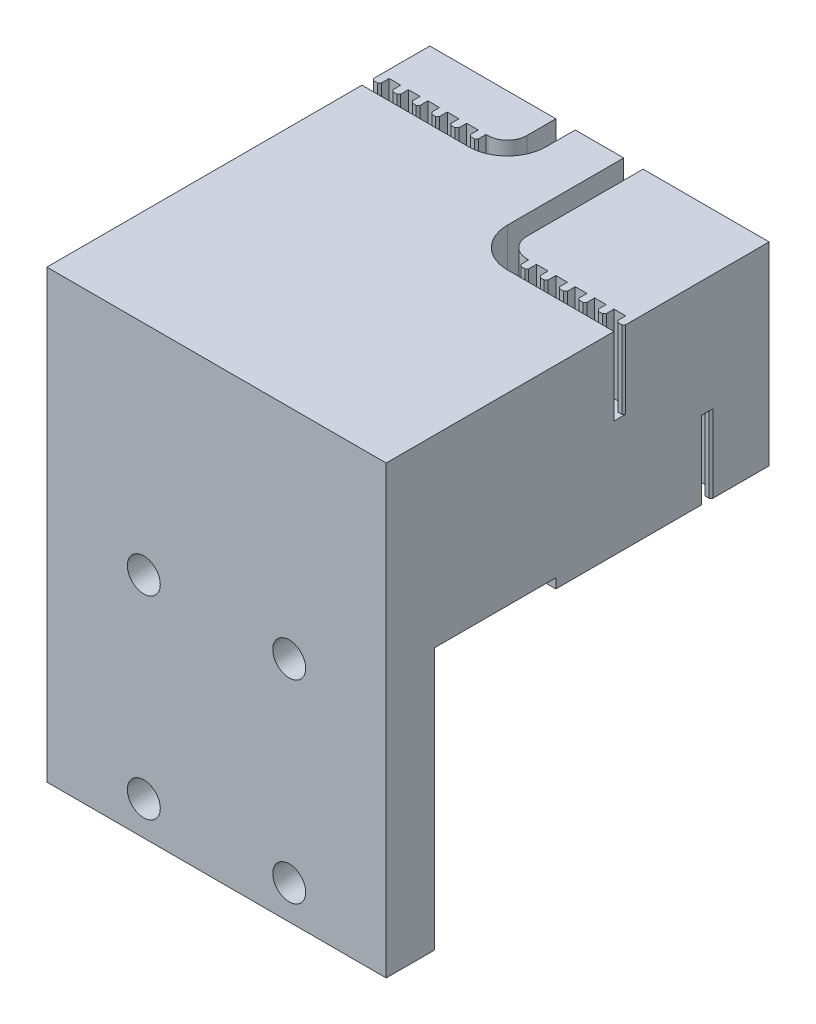
SolidWorks part; units mm, degrees
ref_plane "Front Plane" through (0, 0, 0) normal (0, 0, 1) x (1, 0, 0)
ref_plane "Top Plane" through (0, 0, 0) normal (0, 1, 0) x (1, 0, 0)
ref_plane "Right Plane" through (0, 0, 0) normal (1, 0, 0) x (0, 0, -1)
sketch "Sketch1" plane through (0, 0, 0) normal (0, 1, 0) x (1, 0, 0)
  line L1 (0, 0) -> (35, 0)
  line L2 (0, 0) -> (0, 22)
  line L3 (0, 22) -> (35, 22)
  line L4 (35, 0) -> (35, 22)
  dimension "D1" = 22
  dimension "D2" = 35
extrude "Boss-Extrude1" add sketch "Sketch1" along normal blind 20
sketch "Sketch2" plane through (0, 20, 0) normal (0, 1, 0) x (1, 0, 0)
  line L0 (0, 15) -> (11, 15)
  line L1 (0, 22) -> (0, 0) construction
  line L2 (15, 19) -> (15, 22)
  line L3 (35, 22) -> (0, 22) construction
  line L4 (0, 17) -> (11, 17)
  line L5 (13, 19) -> (13, 22)
  line L6 (35, 6) -> (24, 6)
  line L7 (35, 0) -> (35, 22) construction
  line L8 (20, 10) -> (20, 22)
  line L9 (0, 0) -> (35, 0) construction
  line L10 (22, 22) -> (22, 10)
  line L11 (24, 8) -> (35, 8)
  line L12 (35, 8) -> (35, 6)
  line L13 (0, 15) -> (0, 17)
  line L14 (13, 22) -> (15, 22)
  line L15 (20, 22) -> (22, 22)
  arc A0 (15, 19) -> (11, 15) centre (11, 19) cw
  arc A1 (13, 19) -> (11, 17) centre (11, 19) cw
  arc A2 (20, 10) -> (24, 6) centre (24, 10) ccw
  arc A3 (22, 10) -> (24, 8) centre (24, 10) ccw
  point P9 (15, 15)
  point P15 (13, 17)
  point P29 (20, 6)
  point P32 (22, 8)
  dimension "D3" = 4
  dimension "D6" = 2
  dimension "D11" = 4
  dimension "D12" = 2
  dimension "D1" = 15
  dimension "D2" = 7
  dimension "D4" = 5
  dimension "D5" = 13
  dimension "D7" = 15
  dimension "D8" = 6
  dimension "D9" = 13
  dimension "D10" = 2
extrude "Cut-Extrude1" cut sketch "Sketch2" against normal blind 8
sketch "Sketch5" plane through (0, 0, 0) normal (0, -1, 0) x (-1, 0, 0)
  line L0 (-35, 15) -> (-24, 15)
  line L2 (-20, 19) -> (-20, 22)
  line L4 (-35, 17) -> (-24, 17)
  line L5 (-22, 19) -> (-22, 22)
  line L6 (0, 6) -> (-11, 6)
  line L8 (-15, 10) -> (-15, 22)
  line L10 (-13, 22) -> (-13, 10)
  line L11 (-11, 8) -> (0, 8)
  line L12 (0, 8) -> (0, 6)
  line L13 (-35, 15) -> (-35, 17)
  line L14 (-22, 22) -> (-20, 22)
  line L15 (-15, 22) -> (-13, 22)
  line L16 (-35, 0) -> (-35, 22) construction
  line L17 (-35, 22) -> (0, 22) construction
  line L18 (0, 22) -> (0, 0) construction
  line L19 (0, 0) -> (-35, 0) construction
  arc A0 (-20, 19) -> (-24, 15) centre (-24, 19) cw
  arc A1 (-22, 19) -> (-24, 17) centre (-24, 19) cw
  arc A2 (-15, 10) -> (-11, 6) centre (-11, 10) ccw
  arc A3 (-13, 10) -> (-11, 8) centre (-11, 10) ccw
  point P9 (-20, 15)
  point P15 (-22, 17)
  point P29 (-15, 6)
  point P32 (-13, 8)
  dimension "D3" = 4
  dimension "D6" = 2
  dimension "D11" = 4
  dimension "D12" = 2
  dimension "D1" = 15
  dimension "D2" = 7
  dimension "D4" = 5
  dimension "D5" = 13
  dimension "D7" = 15
  dimension "D8" = 0
  dimension "D9" = 13
  dimension "D10" = 2
  dimension "D13" = 0
  dimension "D14" = 0
  dimension "D15" = 0
  dimension "D16" = 6
extrude "Cut-Extrude2" cut sketch "Sketch5" against normal blind 8
sketch "Sketch6" plane through (0, 20, 0) normal (0, 1, 0) x (1, 0, 0)
  line L0 (0.2, 16) -> (0, 16.2)
  line L1 (0, 17) -> (0.8, 17)
  line L2 (0, 17) -> (0, 16.2)
  line L3 (0.2, 16) -> (0.6, 16)
  line L4 (0.8, 17) -> (0.8, 16.2)
  line L5 (0.6, 16) -> (0.8, 16.2)
  line L6 (2.2, 16) -> (2, 16.2)
  line L7 (2, 17) -> (2.8, 17)
  line L8 (2, 17) -> (2, 16.2)
  line L9 (2.2, 16) -> (2.6, 16)
  line L10 (2.8, 17) -> (2.8, 16.2)
  line L11 (2.6, 16) -> (2.8, 16.2)
  line L12 (4.2, 16) -> (4, 16.2)
  line L13 (4, 17) -> (4.8, 17)
  line L14 (4, 17) -> (4, 16.2)
  line L15 (4.2, 16) -> (4.6, 16)
  line L16 (4.8, 17) -> (4.8, 16.2)
  line L17 (4.6, 16) -> (4.8, 16.2)
  line L18 (6.2, 16) -> (6, 16.2)
  line L19 (6, 17) -> (6.8, 17)
  line L20 (6, 17) -> (6, 16.2)
  line L21 (6.2, 16) -> (6.6, 16)
  line L22 (6.8, 17) -> (6.8, 16.2)
  line L23 (6.6, 16) -> (6.8, 16.2)
  line L24 (8.2, 16) -> (8, 16.2)
  line L25 (8, 17) -> (8.8, 17)
  line L26 (8, 17) -> (8, 16.2)
  line L27 (8.2, 16) -> (8.6, 16)
  line L28 (8.8, 17) -> (8.8, 16.2)
  line L29 (8.6, 16) -> (8.8, 16.2)
  line L30 (10.2, 16) -> (10, 16.2)
  line L31 (10, 17) -> (10.8, 17)
  line L32 (10, 17) -> (10, 16.2)
  line L33 (10.2, 16) -> (10.6, 16)
  line L34 (10.8, 17) -> (10.8, 16.2)
  line L35 (10.6, 16) -> (10.8, 16.2)
  line L36 (34.4, 7) -> (34.2, 7.2)
  line L37 (34.2, 8) -> (35, 8)
  line L38 (34.2, 8) -> (34.2, 7.2)
  line L39 (34.4, 7) -> (34.8, 7)
  line L40 (35, 8) -> (35, 7.2)
  line L41 (34.8, 7) -> (35, 7.2)
  line L42 (35, 8) -> (24, 8) construction
  line L43 (35, 6) -> (35, 8) construction
  line L44 (32.4, 7) -> (32.2, 7.2)
  line L45 (32.2, 8) -> (33, 8)
  line L46 (32.2, 8) -> (32.2, 7.2)
  line L47 (32.4, 7) -> (32.8, 7)
  line L48 (33, 8) -> (33, 7.2)
  line L49 (32.8, 7) -> (33, 7.2)
  line L50 (30.4, 7) -> (30.2, 7.2)
  line L51 (30.2, 8) -> (31, 8)
  line L52 (30.2, 8) -> (30.2, 7.2)
  line L53 (30.4, 7) -> (30.8, 7)
  line L54 (31, 8) -> (31, 7.2)
  line L55 (30.8, 7) -> (31, 7.2)
  line L56 (28.4, 7) -> (28.2, 7.2)
  line L57 (28.2, 8) -> (29, 8)
  line L58 (28.2, 8) -> (28.2, 7.2)
  line L59 (28.4, 7) -> (28.8, 7)
  line L60 (29, 8) -> (29, 7.2)
  line L61 (28.8, 7) -> (29, 7.2)
  line L62 (26.4, 7) -> (26.2, 7.2)
  line L63 (26.2, 8) -> (27, 8)
  line L64 (26.2, 8) -> (26.2, 7.2)
  line L65 (26.4, 7) -> (26.8, 7)
  line L66 (27, 8) -> (27, 7.2)
  line L67 (26.8, 7) -> (27, 7.2)
  line L68 (24.4, 7) -> (24.2, 7.2)
  line L69 (24.2, 8) -> (25, 8)
  line L70 (24.2, 8) -> (24.2, 7.2)
  line L71 (24.4, 7) -> (24.8, 7)
  line L72 (25, 8) -> (25, 7.2)
  line L73 (24.8, 7) -> (25, 7.2)
  point P47 (0, 0)
  point P48 (34.842, 6.9886)
  point P79 (34.395, 6.9929)
  point P80 (0, 0)
  dimension "D1" = 6
  dimension "D2" = 0.8
  dimension "D3" = 0.8
  dimension "D4" = 0
  dimension "D5" = 0
  dimension "D6" = 6
  dimension "D7" = 0.8
  dimension "D8" = 0.8
  dimension "D9" = 0.8
  dimension "D10" = 0.8
  dimension "D11" = 0.2
  dimension "D12" = 0.2
  dimension "D13" = 0.2
extrude "Boss-Extrude2" add sketch "Sketch6" against normal blind 8
sketch "Sketch8" plane through (0, 0, 0) normal (0, -1, 0) x (1, 0, 0)
  line L0 (35, -17) -> (35, -16.2)
  line L1 (35, -17) -> (35, -15) construction
  line L2 (35, -16.2) -> (34.8, -16)
  line L3 (34.8, -16) -> (34.4, -16)
  line L4 (34.4, -16) -> (34.2, -16.2)
  line L5 (34.2, -16.2) -> (34.2, -17)
  line L6 (34.2, -17) -> (35, -17)
  line L7 (33, -17) -> (33, -16.2)
  line L8 (33, -16.2) -> (32.8, -16)
  line L9 (32.8, -16) -> (32.4, -16)
  line L10 (32.4, -16) -> (32.2, -16.2)
  line L11 (32.2, -16.2) -> (32.2, -17)
  line L12 (32.2, -17) -> (33, -17)
  line L13 (31, -17) -> (31, -16.2)
  line L14 (31, -16.2) -> (30.8, -16)
  line L15 (30.8, -16) -> (30.4, -16)
  line L16 (30.4, -16) -> (30.2, -16.2)
  line L17 (30.2, -16.2) -> (30.2, -17)
  line L18 (30.2, -17) -> (31, -17)
  line L19 (29, -17) -> (29, -16.2)
  line L20 (29, -16.2) -> (28.8, -16)
  line L21 (28.8, -16) -> (28.4, -16)
  line L22 (28.4, -16) -> (28.2, -16.2)
  line L23 (28.2, -16.2) -> (28.2, -17)
  line L24 (28.2, -17) -> (29, -17)
  line L25 (27, -17) -> (27, -16.2)
  line L26 (27, -16.2) -> (26.8, -16)
  line L27 (26.8, -16) -> (26.4, -16)
  line L28 (26.4, -16) -> (26.2, -16.2)
  line L29 (26.2, -16.2) -> (26.2, -17)
  line L30 (26.2, -17) -> (27, -17)
  line L31 (25, -17) -> (25, -16.2)
  line L32 (25, -16.2) -> (24.8, -16)
  line L33 (24.8, -16) -> (24.4, -16)
  line L34 (24.4, -16) -> (24.2, -16.2)
  line L35 (24.2, -16.2) -> (24.2, -17)
  line L36 (24.2, -17) -> (25, -17)
  line L37 (0.8, -8) -> (0.8, -7.2)
  line L38 (0.8, -7.2) -> (0.6, -7)
  line L39 (0.6, -7) -> (0.2, -7)
  line L40 (0.2, -7) -> (0, -7.2)
  line L41 (0, -7.2) -> (0, -8)
  line L42 (0, -8) -> (0.8, -8)
  line L43 (0, -8) -> (11, -8) construction
  line L44 (2.8, -8) -> (2.8, -7.2)
  line L45 (2.8, -7.2) -> (2.6, -7)
  line L46 (2.6, -7) -> (2.2, -7)
  line L47 (2.2, -7) -> (2, -7.2)
  line L48 (2, -7.2) -> (2, -8)
  line L49 (2, -8) -> (2.8, -8)
  line L50 (4.8, -8) -> (4.8, -7.2)
  line L51 (4.8, -7.2) -> (4.6, -7)
  line L52 (4.6, -7) -> (4.2, -7)
  line L53 (4.2, -7) -> (4, -7.2)
  line L54 (4, -7.2) -> (4, -8)
  line L55 (4, -8) -> (4.8, -8)
  line L56 (6.8, -8) -> (6.8, -7.2)
  line L57 (6.8, -7.2) -> (6.6, -7)
  line L58 (6.6, -7) -> (6.2, -7)
  line L59 (6.2, -7) -> (6, -7.2)
  line L60 (6, -7.2) -> (6, -8)
  line L61 (6, -8) -> (6.8, -8)
  line L62 (8.8, -8) -> (8.8, -7.2)
  line L63 (8.8, -7.2) -> (8.6, -7)
  line L64 (8.6, -7) -> (8.2, -7)
  line L65 (8.2, -7) -> (8, -7.2)
  line L66 (8, -7.2) -> (8, -8)
  line L67 (8, -8) -> (8.8, -8)
  line L68 (10.8, -8) -> (10.8, -7.2)
  line L69 (10.8, -7.2) -> (10.6, -7)
  line L70 (10.6, -7) -> (10.2, -7)
  line L71 (10.2, -7) -> (10, -7.2)
  line L72 (10, -7.2) -> (10, -8)
  line L73 (10, -8) -> (10.8, -8)
  dimension "D1" = 0.8
  dimension "D2" = 0.2
  dimension "D3" = 0.8
  dimension "D4" = 0.8
  dimension "D5" = 0.2
  dimension "D6" = 6
  dimension "D7" = 0.8
  dimension "D8" = 0.2
  dimension "D9" = 0.8
  dimension "D10" = 0.8
  dimension "D11" = 0.2
  dimension "D12" = 0
  dimension "D13" = 0
  dimension "D14" = 6
extrude "Boss-Extrude4" add sketch "Sketch8" against normal blind 8
sketch "Sketch9" plane through (0, 0, 0) normal (0, 0, 1) x (1, 0, 0)
  line L1 (0, 20) -> (35, 20)
  line L2 (0, 20) -> (0, 1)
  line L3 (0, 1) -> (35, 1)
  line L4 (35, 20) -> (35, 1)
  line L5 (35, 20) -> (35, 0) construction
  dimension "D1" = 19
  dimension "D2" = 35
extrude "Boss-Extrude5" add sketch "Sketch9" along normal blind 12.5
sketch "Sketch11" plane through (0, 0, 12.5) normal (0, 0, 1) x (1, 0, 0)
  line L1 (0, 20) -> (35, 20)
  line L2 (0, 20) -> (0, -26)
  line L3 (0, -26) -> (35, -26)
  line L4 (35, 20) -> (35, -26)
  dimension "D1" = 46
  dimension "D2" = 35
extrude "Boss-Extrude6" add sketch "Sketch11" along normal blind 5
sketch "Sketch12" plane through (0, 0, 17.5) normal (0, 0, 1) x (1, 0, 0)
  line L0 (0, 20) -> (0, -26) construction
  line L1 (0, -26) -> (35, -26) construction
  line L3 (35, 20) -> (0, 20) construction
  circle A0 centre (10, -2.5) radius 1.7
  circle A1 centre (25, -2.5) radius 1.7
  circle A2 centre (25, -22.5) radius 1.7
  circle A3 centre (10, -22.5) radius 1.7
  point P0 (17.5, -12.5)
  dimension "D3" = 3.4
  dimension "D4" = 7.5
  dimension "D1" = 17.5
  dimension "D2" = 13.5
  dimension "D5" = 10
  dimension "D7" = 46
  dimension "D6" = 2
extrude "Cut-Extrude3" cut sketch "Sketch12" against normal blind 5
